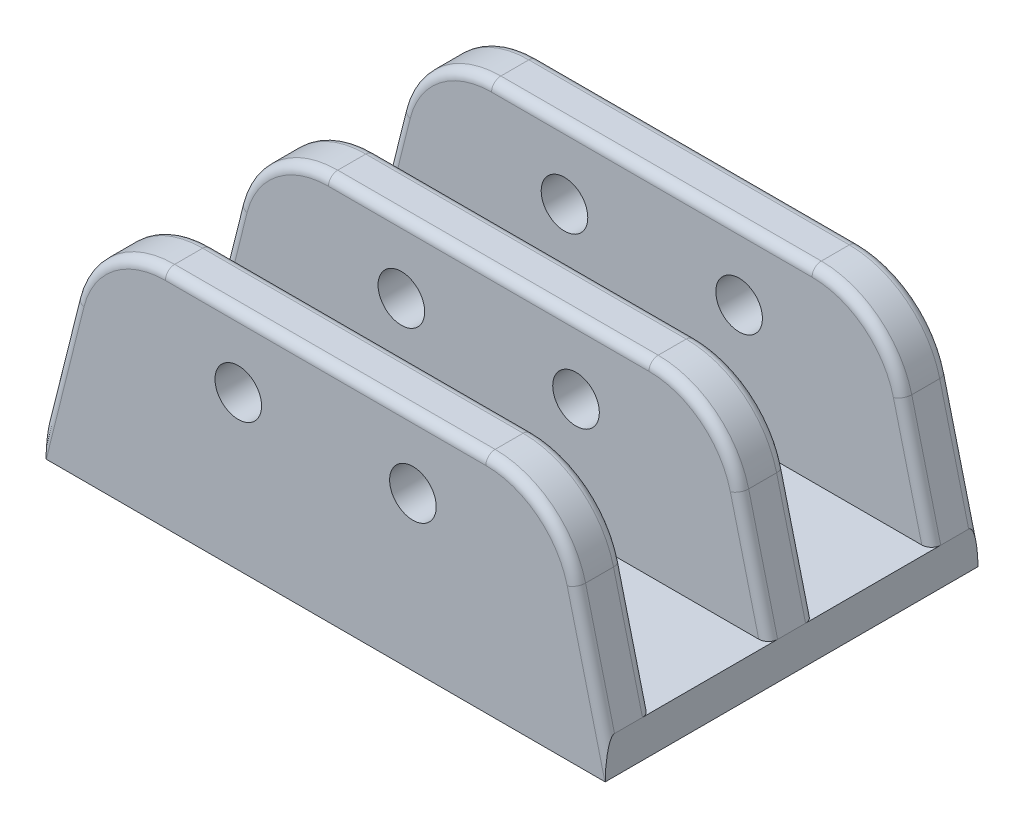
SolidWorks part; units mm, degrees
ref_plane "Front Plane" through (0, 0, 0) normal (0, 0, 1) x (1, 0, 0)
ref_plane "Top Plane" through (0, 0, 0) normal (0, 1, 0) x (1, 0, 0)
ref_plane "Right Plane" through (0, 0, 0) normal (1, 0, 0) x (0, 0, -1)
sketch "Sketch1" plane through (0, 0, 0) normal (0, 1, 0) x (1, 0, 0)
  line L1 (-9.75, -14.75) -> (9.75, -14.75)
  line L2 (-9.75, -14.75) -> (-9.75, 14.75)
  line L3 (-9.75, 14.75) -> (9.75, 14.75)
  line L4 (9.75, -14.75) -> (9.75, 14.75)
  line L5 (-9.75, -14.75) -> (9.75, 14.75) construction
  line L6 (-9.75, 14.75) -> (9.75, -14.75) construction
  point P0 (0, 0)
  dimension "D1" = 19.5
  dimension "D2" = 29.5
extrude "Boss-Extrude1" add sketch "Sketch1" along normal blind 4 contours L2 L1 L4 L3
sketch "Sketch2" plane through (0, 4, 0) normal (0, 1, 0) x (1, 0, 0)
  line L1 (-30, -20) -> (30, -20)
  line L2 (-30, -20) -> (-30, 20)
  line L3 (-30, 20) -> (30, 20)
  line L4 (30, -20) -> (30, 20)
  line L5 (-30, -20) -> (30, 20) construction
  line L6 (-30, 20) -> (30, -20) construction
  point P0 (0, 0)
  dimension "D1" = 60
  dimension "D2" = 40
extrude "Boss-Extrude3" add sketch "Sketch2" along normal blind 4
sketch "Sketch3" plane through (0, 8, 0) normal (0, 1, 0) x (1, 0, 0)
  line L0 (30, -20) -> (30, 20) construction
  line L1 (-30, 20) -> (30, 20)
  line L2 (-30, 20) -> (-30, 15)
  line L3 (-30, 15) -> (30, 15)
  line L4 (30, 20) -> (30, 15)
  line L6 (30, -20) -> (30, -15)
  line L7 (-30, -15) -> (30, -15)
  line L8 (-30, -20) -> (-30, -15)
  line L9 (-30, -20) -> (30, -20)
  line M9 (30, -20) -> (30, 20)
  line M10 (30, 20) -> (-30, 20)
  line M11 (-30, 20) -> (-30, -20)
  dimension "D1" = 5
extrude "Boss-Extrude4" add sketch "Sketch3" along normal blind 20 contours L3 M11 M9 M10 | L6 L7 L8 L9 region at (0, 8, -17.5)
chamfer "Chamfer1" distance 5 distance2 20 1 edges at (-30, 28, 17.5) first distance on face at (0, 28, 17.5)
chamfer "Chamfer2" distance 20 distance2 5 1 edges at (-30, 28, -17.5) first distance on face at (-30, 12.5714, -2.1429)
chamfer "Chamfer3" distance 20 distance2 5 2 edges at (30, 28, -17.5) (30, 28, 17.5) first distance on face at (30, 17, 0)
fillet "Fillet1" radius 10 4 edges at (25, 28, 17.5) (25, 28, -17.5) (-25, 28, 17.5) (-25, 28, -17.5)
fillet "Fillet2" radius 1 10 edges at (28.4468, 14.2127, -20) (23.3464, 25.8821, -20) (-28.4468, 14.2127, -20) (-23.3464, 25.8821, -20) (-28.4468, 14.2127, 20) (-23.3464, 25.8821, 20) (28.4468, 14.2127, 20) (23.3464, 25.8821, 20) (0, 28, -20) (0, 28, 20)
sketch "Sketch4" plane through (0, 8, 0) normal (0, 1, 0) x (1, 0, 0)
  line L0 (30, -15) -> (30, 15) construction
  line L1 (-30, 2.5) -> (30, 2.5)
  line L2 (-30, 2.5) -> (-30, -2.5)
  line L3 (-30, -2.5) -> (30, -2.5)
  line L4 (30, 2.5) -> (30, -2.5)
  line L5 (-30, 2.5) -> (30, -2.5) construction
  line L6 (-30, -2.5) -> (30, 2.5) construction
  point P0 (0, 0)
  dimension "D1" = 5
extrude "Boss-Extrude5" add sketch "Sketch4" along normal blind 20
chamfer "Chamfer4" distance 20 distance2 5 2 edges at (30, 28, 0) (-30, 28, 0) first distance on face at (30, 11.3671, 0) first distance on face at (-30, 11.3671, 0)
fillet "Fillet3" radius 10 2 edges at (-25, 28, 0) (25, 28, 0)
fillet "Fillet4" radius 1 10 edges at (28.4468, 14.2127, -2.5) (23.3464, 25.8821, -2.5) (-28.4468, 14.2127, -2.5) (-23.3464, 25.8821, -2.5) (-28.4468, 14.2127, 2.5) (-23.3464, 25.8821, 2.5) (28.4468, 14.2127, 2.5) (23.3464, 25.8821, 2.5) (0, 28, -2.5) (0, 28, 2.5)
fillet "Fillet5" radius 1 10 edges at (-28.4468, 14.2127, 15) (-23.3464, 25.8821, 15) (28.4468, 14.2127, 15) (23.3464, 25.8821, 15) (-28.4468, 14.2127, -15) (-23.3464, 25.8821, -15) (28.4468, 14.2127, -15) (23.3464, 25.8821, -15) (0, 28, 15) (0, 28, -15)
sketch "Sketch5" plane through (0, 0, 20) normal (0, 0, 1) x (1, 0, 0)
  line L0 (17.1922, 27) -> (-17.1922, 27) construction
  circle A0 centre (-9.3692, 20.5) radius 2.5
  circle A1 centre (9.3692, 20.5) radius 2.5
  dimension "D1" = 6.5
  dimension "D2" = 20.6
extrude "Cut-Extrude1" cut sketch "Sketch5" against normal through all contours A0 | A1
